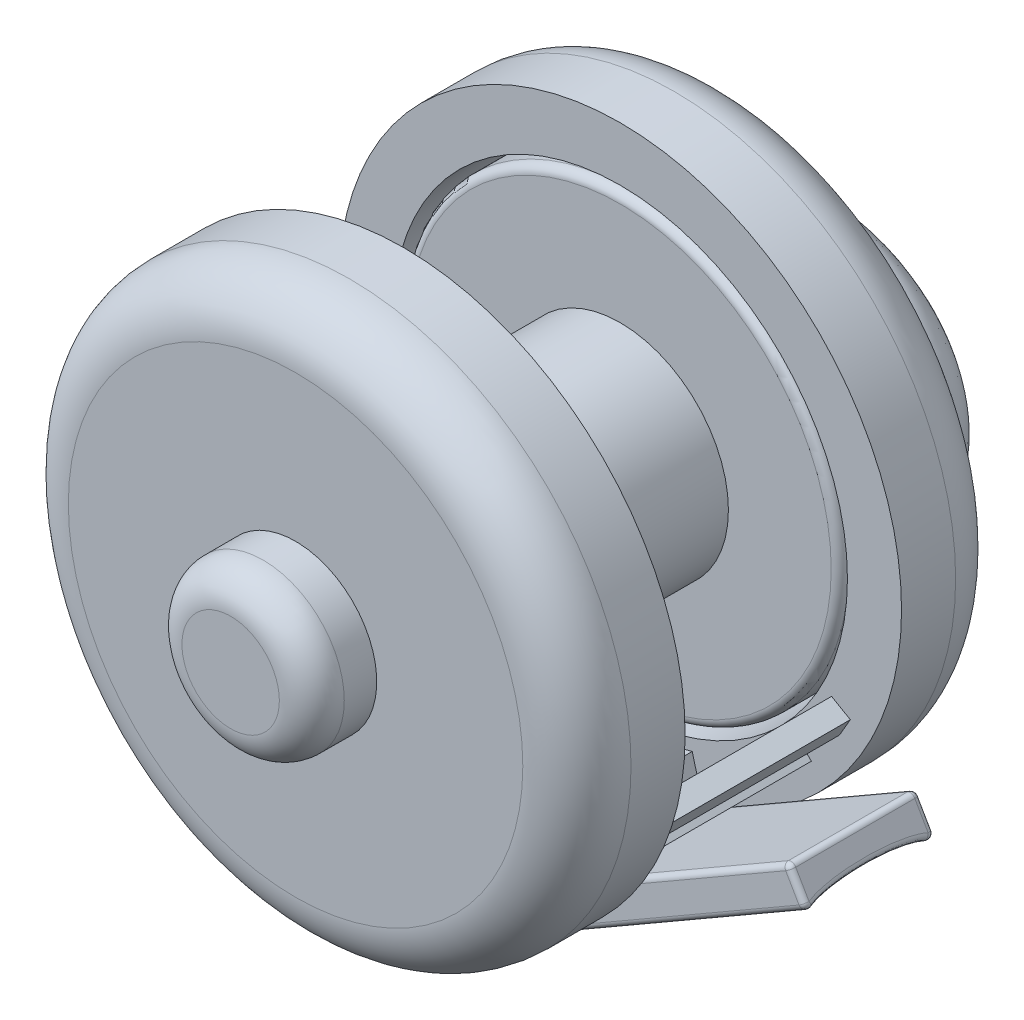
SolidWorks part; units mm, degrees
ref_plane "Front Plane" through (0, 0, 0) normal (0, 0, 1) x (1, 0, 0)
ref_plane "Top Plane" through (0, 0, 0) normal (0, 1, 0) x (1, 0, 0)
ref_plane "Right Plane" through (0, 0, 0) normal (1, 0, 0) x (0, 0, -1)
sketch "Sketch1" plane through (0, 0, 0) normal (0, 0, 1) x (1, 0, 0)
  circle A0 centre (0, 0) radius 33.02
  dimension "D1" = 66.04
extrude "Boss-Extrude1" add sketch "Sketch1" along normal blind 12.7
sketch "Sketch2" plane through (0, 0, 12.7) normal (0, 0, 1) x (1, 0, 0)
  circle A0 centre (0, 0) radius 26.67
  dimension "D1" = 53.34
extrude "Cut-Extrude1" cut sketch "Sketch2" against normal blind 11.43
sketch "Sketch3" plane through (0, 0, 1.27) normal (0, 0, 1) x (1, 0, 0)
  circle A0 centre (0, 0) radius 25.781
  dimension "D1" = 51.562
extrude "Boss-Extrude3" add sketch "Sketch3" along normal blind 11.43
sketch "Sketch4" plane through (0, 0, 12.7) normal (0, 0, 1) x (1, 0, 0)
  circle A0 centre (0, 0) radius 12.7
  dimension "D1" = 25.4
extrude "Boss-Extrude4" add sketch "Sketch4" along normal blind 25.4
sketch "Sketch5" plane through (0, 0, 38.1) normal (0, 0, 1) x (1, 0, 0)
  circle A0 centre (0, 0) radius 33.02
  dimension "D1" = 66.04
extrude "Boss-Extrude5" add sketch "Sketch5" along normal blind 12.7
sketch "Sketch7" plane through (0, 0, 38.1) normal (0, 0, -1) x (-1, 0, 0)
  circle A0 centre (0, 0) radius 33.02
  dimension "D1" = 66.04
sketch "Sketch9" plane through (0, 0, 38.1) normal (0, 0, -1) x (-1, 0, 0)
  circle A0 centre (0, 0) radius 26.67
  dimension "D1" = 53.34
extrude "Cut-Extrude4" cut sketch "Sketch9" against normal blind 11.43
sketch "Sketch10" plane through (0, 0, 38.1) normal (0, 0, -1) x (-1, 0, 0)
  circle A0 centre (0, 0) radius 25.781
  dimension "D1" = 51.562
extrude "Boss-Extrude8" add sketch "Sketch10" against normal blind 11.43
fillet "Fillet1" radius 1.016 2 edges at (-25.781, 0, 38.1) (25.781, 0, 12.7)
fillet "Fillet2" radius 6.35 1 edges at (33.02, 0, 0) type face fillet first side face at (33.02, 0, 0) second side face at (33.02, 0, 12.7)
fillet "Fillet3" radius 6.35 1 edges at (33.02, 0, 50.8) type face fillet first side face at (33.02, 0, 50.8) second side face at (33.02, 0, 50.8)
sketch "Sketch11" plane through (0, 0, 50.8) normal (0, 0, 1) x (1, 0, 0)
  circle A0 centre (0, 0) radius 9.525
  dimension "D1" = 19.05
extrude "Boss-Extrude9" add sketch "Sketch11" along normal blind 7.62
fillet "Fillet4" radius 3.81 1 edges at (9.525, 0, 58.42)
sketch "Sketch12" plane through (0, 0, 0) normal (0, 0, -1) x (-1, 0, 0)
  ellipse E0 centre (0, 0) end of major axis (22.5458, -10.9778) minor radius 19.7085
extrude "Boss-Extrude10" add sketch "Sketch12" along normal blind 6.35
fillet "Fillet5" radius 3.81 1 edges at (-22.5458, -10.9778, -6.35)
sketch "Sketch14" plane through (0, 0, 38.1) normal (0, 0, -1) x (-1, 0, 0)
  line L5 (-8.4507, -26.6606) -> (-5.9973, -27.318)
  line L6 (-8.4507, -26.6606) -> (-9.1081, -29.114)
  line L11 (-9.1081, -29.114) -> (-6.6547, -29.7714)
  line L12 (-5.9973, -27.318) -> (-6.6547, -29.7714)
  line L18 (-9.1081, -29.114) -> (-6.6547, -29.7714)
  line L19 (-8.4507, -26.6606) -> (-5.9973, -27.318)
  line L22 (-8.4507, -26.6606) -> (-6.6547, -29.7714) construction
  line L23 (-9.1081, -29.114) -> (-5.9973, -27.318) construction
  line L29 (-15.0556, -23.5663) -> (-12.8559, -24.8363)
  line L30 (-1.27, -27.94) -> (1.27, -27.94)
  line L31 (-1.27, -27.94) -> (-1.27, -30.48)
  line L32 (-1.27, -30.48) -> (1.27, -30.48)
  line L33 (1.27, -27.94) -> (1.27, -30.48)
  line L34 (-1.27, -27.94) -> (1.27, -30.48) construction
  line L35 (-1.27, -30.48) -> (1.27, -27.94) construction
  line L40 (-15.0556, -23.5663) -> (-16.3256, -25.766)
  line L46 (-16.3256, -25.766) -> (-14.1259, -27.036)
  line L47 (-12.8559, -24.8363) -> (-14.1259, -27.036)
  line L49 (-16.3256, -25.766) -> (-14.1259, -27.036)
  line L50 (-15.0556, -23.5663) -> (-12.8559, -24.8363)
  line L52 (-1.27, -30.48) -> (1.27, -30.48)
  line L53 (-15.0556, -23.5663) -> (-14.1259, -27.036) construction
  line L54 (-16.3256, -25.766) -> (-12.8559, -24.8363) construction
  line L55 (-1.27, -27.94) -> (1.27, -27.94)
  line L56 (-20.6346, -18.8679) -> (-18.8385, -20.664)
  line L57 (-20.6346, -18.8679) -> (-22.4306, -20.664)
  line L58 (-22.4306, -20.664) -> (-20.6346, -22.46)
  line L59 (-18.8385, -20.664) -> (-20.6346, -22.46)
  line L60 (-22.4306, -20.664) -> (-20.6346, -22.46)
  line L61 (-20.6346, -18.8679) -> (-18.8385, -20.664)
  line L62 (-20.6346, -18.8679) -> (-20.6346, -22.46) construction
  line L63 (-22.4306, -20.664) -> (-18.8385, -20.664) construction
  line L64 (-24.8074, -12.8857) -> (-23.5374, -15.0854)
  line L65 (-24.8074, -12.8857) -> (-27.0072, -14.1557)
  line L66 (-27.0072, -14.1557) -> (-25.7372, -16.3554)
  line L67 (-23.5374, -15.0854) -> (-25.7372, -16.3554)
  line L68 (-27.0072, -14.1557) -> (-25.7372, -16.3554)
  line L69 (-24.8074, -12.8857) -> (-23.5374, -15.0854)
  line L70 (-24.8074, -12.8857) -> (-25.7372, -16.3554) construction
  line L71 (-27.0072, -14.1557) -> (-23.5374, -15.0854) construction
  point P0 (0, -29.21)
  point P4 (-7.5527, -28.216)
  point P5 (-7.5527, -28.216)
  point P11 (-14.5908, -25.3011)
  point P12 (-14.5908, -25.3011)
  point P17 (-20.6346, -20.664)
  point P18 (-20.6346, -20.664)
  point P23 (-25.2723, -14.6205)
  point P24 (-25.2723, -14.6205)
  point P29 (0, -29.21)
  point P34 (0, 0)
  dimension "D2" = 5
  dimension "D12" = 2.54
extrude "Boss-Extrude11" add sketch "Sketch14" along normal blind 25.4 contours L33 L30 L31 L32 | L47 L40 | L12 L5 L6 L11 | L59 L56 L57 L58 | L67 L64 L65 L66 region at (7.5527, -28.216, 38.1) region at (14.5908, -25.3011, 38.1) region at (0, -29.21, 38.1) region at (20.6346, -20.664, 38.1) region at (25.2723, -14.6205, 38.1)
sketch "Sketch15" plane through (15.2384, -26.3937, 0) normal (0.5, -0.866, 0) x (-0.866, -0.5, 0)
  line L1 (-28.5604, -33.02) -> (28.5896, -33.02)
  line L2 (-28.5604, -33.02) -> (-28.5604, -17.78)
  line L3 (-28.5604, -17.78) -> (28.5896, -17.78)
  line L4 (28.5896, -33.02) -> (28.5896, -17.78)
  line L5 (-28.5604, -33.02) -> (28.5896, -17.78) construction
  line L6 (-28.5604, -17.78) -> (28.5896, -33.02) construction
  line L7 (1.2846, -12.7) -> (1.2846, -38.1) construction
  point P0 (0.0146, -25.4)
  dimension "D1" = 1.27
  dimension "D2" = 15.24
  dimension "D3" = 57.15
extrude "Boss-Extrude12" add sketch "Sketch15" along normal blind 5.08
sketch "Sketch16" plane through (24.734, 14.2802, 0) normal (0.866, 0.5, 0) x (0, 0, -1)
  line L0 (-17.78, -35.5568) -> (-33.02, -35.5568) construction
  ellipse E0 centre (-25.4, -35.5568) end of major axis (-17.78, -35.5568) minor radius 1.5875
  dimension "D1" = 3.175
extrude "Cut-Extrude5" cut sketch "Sketch16" against normal through all
fillet "Fillet6" radius 0.635 14 edges at (41.2424, -14.3132, 33.02) (41.2424, -14.3132, 17.78) (39.9724, -12.1135, 25.4) (41.7187, -15.1381, 25.4) (28.149, -18.9397, 33.02) (28.149, -18.9397, 17.78) (17.7658, -30.8004, 17.78) (17.7658, -30.8004, 33.02) (2.3025, -33.8622, 33.02) (2.3025, -33.8622, 17.78) (-8.2509, -42.8882, 17.78) (-9.5209, -40.6885, 25.4) (-8.2509, -42.8882, 33.02) (-7.7747, -43.7131, 25.4)
